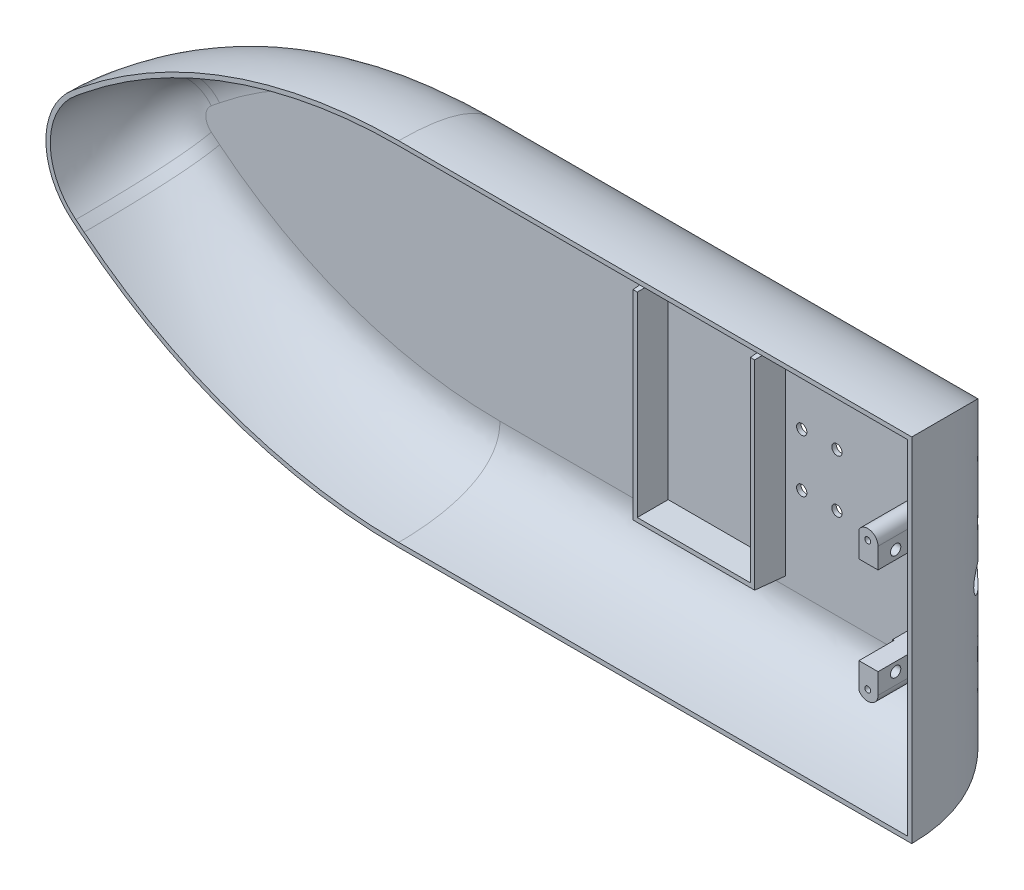
SolidWorks part; units mm, degrees
ref_plane "Plan de face" through (0, 0, 0) normal (0, 0, 1) x (1, 0, 0)
ref_plane "Plan de dessus" through (0, 0, 0) normal (0, 1, 0) x (1, 0, 0)
ref_plane "Plan de droite" through (0, 0, 0) normal (1, 0, 0) x (0, 0, -1)
sketch "Esquisse1" plane through (0, 0, 0) normal (0, 0, 1) x (1, 0, 0)
  line L0 (-4.3509, 33.8649) -> (-99.546, 33.8649) construction
  line L1 (150.454, 73.8649) -> (-4.3509, 73.8649)
  line L2 (150.454, 73.8649) -> (150.454, -6.1351)
  line L3 (150.454, -6.1351) -> (-4.3509, -6.1351)
  line L4 (-4.3509, 73.8649) -> (-4.3509, 33.8649) construction
  line L5 (-102.6925, 37.7506) -> (-99.8611, 40.0435)
  line L6 (-102.6925, 29.9791) -> (-99.8611, 27.6863)
  line L7 (-4.3509, 33.8649) -> (-4.3509, -6.1351) construction
  arc A0 (-102.6925, 37.7506) -> (-102.6925, 29.9791) centre (-99.546, 33.8649) ccw
  arc A1 (-4.3509, 73.8649) -> (-99.8611, 40.0435) centre (-4.3509, -77.9041) ccw
  arc A2 (-99.8611, 27.6863) -> (-4.3509, -6.1351) centre (-4.3509, 145.6338) ccw
  dimension "D3" = 10
  dimension "D1" = 250
  dimension "D2" = 80
extrude "Boss.-Extru.1" add sketch "Esquisse1" along normal blind 1.5
sketch "Esquisse3" plane through (0, 0, 1.5) normal (0, 0, 1) x (1, 0, 0)
  line L0 (150.454, 33.8649) -> (-104.546, 33.8649) construction
  line L1 (150.454, -6.1351) -> (150.454, 73.8649) construction
  line L2 (110.454, 66.3622) -> (110.454, 22.1054) construction
  line L3 (98.454, 66.3622) -> (98.454, 22.1054) construction
  arc A0 (-102.6925, 37.7506) -> (-102.6925, 29.9791) centre (-99.546, 33.8649) ccw construction
  circle A1 centre (98.454, 42.8649) radius 1.75
  circle A2 centre (98.454, 24.8649) radius 1.75
  circle A3 centre (110.454, 24.8649) radius 1.75
  circle A4 centre (110.454, 42.8649) radius 1.75
  dimension "D1" = 3.5
  dimension "D2" = 3.5
  dimension "D3" = 3.5
  dimension "D4" = 3.5
  dimension "D7" = 9
  dimension "D8" = 9
  dimension "D9" = 9
  dimension "D5" = 12
  dimension "D6" = 9
  dimension "D10" = 40
extrude "Enlèv. mat.-Extru.1" cut sketch "Esquisse3" against normal up to next
sketch "Esquisse4" plane through (0, 0, 1.5) normal (0, 0, -1) x (-1, 0, 0)
  line L0 (-150.454, 33.8649) -> (-3.0389, 33.8649) construction
  line L1 (-52.954, -0.6351) -> (-90.454, -0.6351)
  line L2 (-52.954, -0.6351) -> (-52.954, 65.8649)
  line L3 (-55.454, 68.3649) -> (-87.954, 68.3649)
  line L5 (-150.454, -6.1351) -> (-150.454, 73.8649) construction
  line L7 (-50.454, -3.1351) -> (-92.954, -3.1351)
  line L8 (-50.454, -3.1351) -> (-50.454, 65.8649)
  line L9 (-55.454, 70.8649) -> (-87.954, 70.8649)
  line L10 (-92.954, -3.1351) -> (-92.954, 65.8649)
  line L11 (-90.454, -0.6351) -> (-90.454, 65.8649)
  line L13 (-50.454, 65.8649) -> (-52.954, 65.8649)
  line L14 (-55.454, 70.8649) -> (-55.454, 68.3649)
  line L17 (-92.954, 65.8649) -> (-90.454, 65.8649)
  line L18 (-87.954, 70.8649) -> (-87.954, 68.3649)
  circle A0 centre (-98.454, 24.8649) radius 1.75 construction
  point P3 (-70.3996, 0.9688)
  point P4 (-51.6001, 33.8649)
  point P14 (-70.3501, 69.9688)
  dimension "D2" = 2.5
  dimension "D3" = 2.5
  dimension "D4" = 2.5
  dimension "D5" = 34.5
  dimension "D6" = 5.5
  dimension "D7" = 2.5
  dimension "D8" = 32.5
  dimension "D9" = 2.5
  dimension "D10" = 2.5
  dimension "D11" = 34.5
  dimension "D12" = 2.5
  dimension "D13" = 2.5
extrude "Boss.-Extru.2" add sketch "Esquisse4" against normal blind 10 draft 3
sketch "Esquisse7" plane through (150.454, 0, 0) normal (1, 0, 0) x (0, 0, -1)
  line L0 (0, -6.1351) -> (0, 73.8649) construction
  line L1 (-1.5, -6.1351) -> (-1.5, 73.8649) construction
  line L4 (-1.5, 73.8649) -> (0, 73.8649) construction
  line L6 (-1.5, 73.8649) -> (0, 73.8649)
  line L7 (-36, 93.8649) -> (-36, 92.3649)
  spline S0 degree 3 poles (0, 73.8649) (0, 81.3378) (-5.0996, 93.8032) (-36, 93.8649) knots 0 0 0 0 1 1 1 1
  spline S1 degree 3 poles (-36, 92.3649) (-32.8249, 92.3649) (-1.5, 92.9097) (-1.5, 73.8649) knots 0 0 0 0 1 1 1 1
  dimension "D2" = 20
  dimension "D1" = 36
sweep "Balayage1" add profiles "Esquisse7" path "Esquisse1<2>"
sketch "Esquisse1<2>" plane through (0, 0, 0) normal (0, 0, 1) x (1, 0, 0) same geometry as "Esquisse1"
sketch "Esquisse8" plane through (0, 0, 0) normal (0, 0, -1) x (-1, 0, 0)
  line L0 (-150.454, 33.8649) -> (-183.7283, 33.8649) construction
  line L2 (-155.454, 64.6793) -> (-155.454, 3.4231) construction
  line L3 (-150.454, 73.8649) -> (-150.454, -6.1351) construction
  line L4 (-150.454, -6.1351) -> (-150.454, 73.8649) construction
  circle A0 centre (-155.454, 55.8649) radius 1
  circle A1 centre (-155.454, 11.8649) radius 1
  point P2 (-150.454, 33.8649)
  dimension "D3" = 2
  dimension "D4" = 2
  dimension "D1" = 22
  dimension "D2" = 22
  dimension "D5" = 5
extrude "Enlèv. mat.-Extru.2" cut sketch "Esquisse8" against normal up to next
sketch "Esquisse9" plane through (0, 0, 36) normal (0, 0, 1) x (1, 0, 0)
  line L2 (151.954, 55.8649) -> (151.954, 48.8649)
  line L3 (151.954, 48.8649) -> (158.954, 48.8649)
  line L4 (158.954, 55.8649) -> (158.954, 48.8649)
  line L6 (158.954, 11.8649) -> (158.954, 18.8649)
  line L7 (158.954, 18.8649) -> (151.954, 18.8649)
  line L8 (151.954, 11.8649) -> (151.954, 18.8649)
  circle A0 centre (155.454, 55.8649) radius 1
  circle A1 centre (155.454, 11.8649) radius 1
  arc A2 (151.954, 11.8649) -> (158.954, 11.8649) centre (155.454, 11.8649) ccw
  arc A3 (158.954, 55.8649) -> (151.954, 55.8649) centre (155.454, 55.8649) ccw
  dimension "D1" = 2.5
  dimension "D2" = 2.5
  dimension "D3" = 2
  dimension "D4" = 2
  dimension "D5" = 30
extrude "Boss.-Extru.3" add sketch "Esquisse9" against normal up to next
sketch "Esquisse10" plane through (0, 0, 36) normal (0, 0, 1) x (1, 0, 0)
  line L0 (152.454, 10.0621) -> (152.454, 18.8649)
  line L2 (152.454, 48.8649) -> (152.454, 57.6676)
  line L3 (151.954, 48.8649) -> (158.954, 48.8649) construction
  line L4 (151.954, 55.8649) -> (151.954, 48.8649) construction
  line L5 (151.954, 55.8649) -> (151.954, 48.8649)
  line L6 (152.454, 48.8649) -> (151.954, 48.8649)
  line L7 (158.954, 18.8649) -> (151.954, 18.8649) construction
  line L8 (151.954, 18.8649) -> (151.954, 11.8649) construction
  line L9 (152.454, 18.8649) -> (151.954, 18.8649)
  line L10 (151.954, 18.8649) -> (151.954, 11.8649)
  line L11 (150.454, 73.8649) -> (150.454, -6.1351) construction
  circle A0 centre (155.454, 55.8649) radius 3.5 construction
  circle A1 centre (155.454, 11.8649) radius 3.5 construction
  arc A2 (158.954, 55.8649) -> (151.954, 55.8649) centre (155.454, 55.8649) ccw construction
  arc A3 (151.954, 11.8649) -> (158.954, 11.8649) centre (155.454, 11.8649) ccw construction
  arc A4 (152.454, 57.6676) -> (151.954, 55.8649) centre (155.454, 55.8649) ccw
  arc A5 (151.954, 11.8649) -> (152.454, 10.0621) centre (155.454, 11.8649) ccw
  dimension "D1" = 2
extrude "Enlèv. mat.-Extru.3" cut sketch "Esquisse10" against normal blind 12
sketch "Esquisse11" plane through (152.454, 0, 0) normal (-1, 0, 0) x (0, 0, 1)
  line L0 (30, 48.8649) -> (30, 18.8649) construction
  line L4 (24, 48.8649) -> (36, 48.8649) construction
  line L5 (24, 18.8649) -> (36, 18.8649) construction
  line L6 (30, 48.8649) -> (30, 51.8649) construction
  line L7 (30, 15.8649) -> (30, 18.8649) construction
  circle A0 centre (30, 51.8649) radius 1.75
  circle A1 centre (30, 15.8649) radius 1.75
  point P6 (30, 48.8649)
  point P7 (30, 18.8649)
  dimension "D1" = 3.5
  dimension "D2" = 3.5
  dimension "D3" = 36
extrude "Enlèv. mat.-Extru.4" cut sketch "Esquisse11" against normal up to next
sketch "Esquisse16" plane through (151.954, 0, 0) normal (-1, 0, 0) x (0, 0, 1)
  line L0 (1.5673, 48.8649) -> (1.5673, 55.8649) construction
  line L1 (1.5673, 39.8649) -> (16.5673, 39.8649)
  line L2 (1.5673, 39.8649) -> (1.5673, 27.8649)
  line L3 (1.5673, 27.8649) -> (16.5673, 27.8649)
  line L4 (16.5673, 39.8649) -> (16.5673, 27.8649)
  line L6 (1.5673, 48.8649) -> (24, 48.8649) construction
  line L7 (1.5673, 18.8649) -> (24, 18.8649) construction
  line L8 (16.5673, 39.8649) -> (16.5673, 48.8649) construction
  line L9 (16.5673, 27.8649) -> (16.5673, 18.8649) construction
  dimension "D1" = 15
  dimension "D2" = 12
extrude "Boss.-Extru.4" add sketch "Esquisse16" against normal up to surface (14.6088 mm away) up to face at (155.6848, 14.4901, 2.6996)
sketch "Esquisse12" plane through (201.4029, 0, -73.3047) normal (0.9397, 0, -0.342) x (-0.342, 0, -0.9397)
  circle A0 centre (-61.7525, 33.8649) radius 4.25
  dimension "D1" = 8.5
extrude "Enlèv. mat.-Extru.5" cut sketch "Esquisse12" against normal up to surface (73.5516 mm away) up to face at (151.954, 33.8649, 9.0673)
sketch "Esquisse17" plane through (0, 0, 16.5673) normal (0, 0, 1) x (1, 0, 0)
  line L0 (166.5628, 39.8649) -> (151.954, 39.8649) construction
  line L1 (156.954, 39.8649) -> (160.954, 39.8649)
  line L2 (156.954, 39.8649) -> (156.954, 27.8649)
  line L3 (156.954, 27.8649) -> (160.954, 27.8649)
  line L4 (160.954, 39.8649) -> (160.954, 27.8649)
  line L5 (166.5628, 27.8649) -> (151.954, 27.8649) construction
  line L6 (151.954, 27.8649) -> (151.954, 39.8649) construction
  point P8 (151.954, 33.8649)
  dimension "D1" = 4
  dimension "D2" = 5
extrude "Enlèv. mat.-Extru.6" cut sketch "Esquisse17" against normal blind 8
